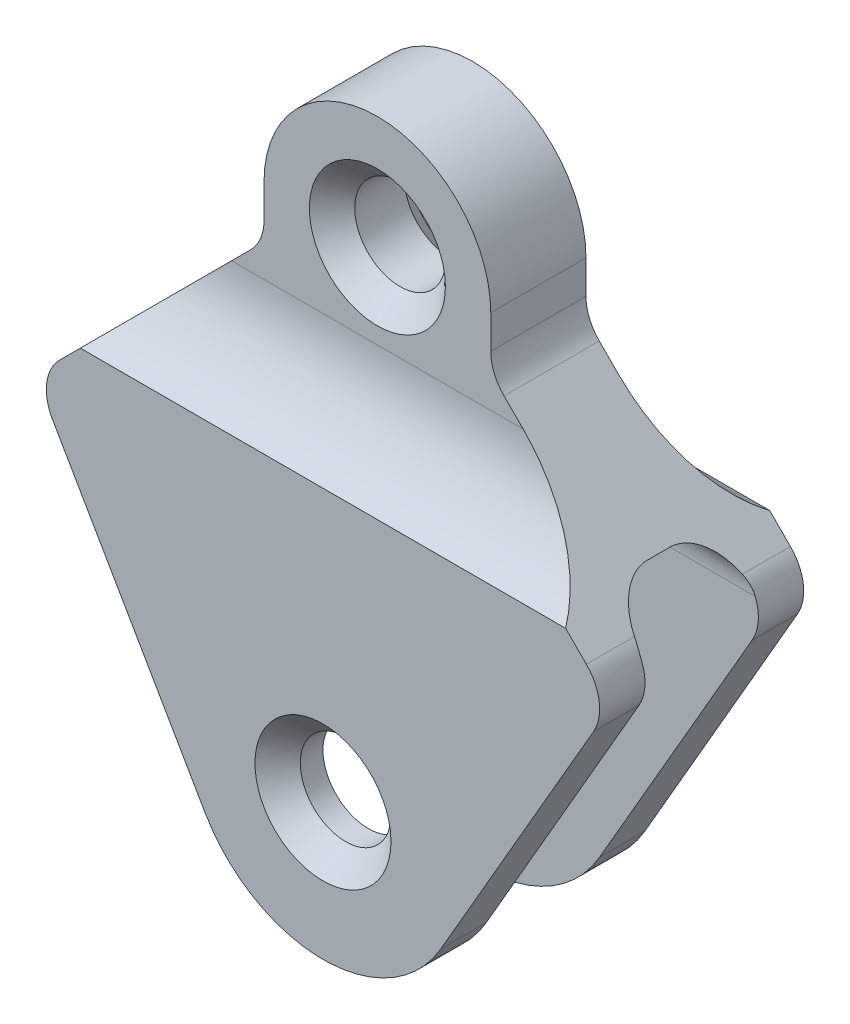
SolidWorks part; units mm, degrees
ref_plane "Front Plane" through (0, 0, 0) normal (0, 0, 1) x (1, 0, 0)
ref_plane "Top Plane" through (0, 0, 0) normal (0, 1, 0) x (1, 0, 0)
ref_plane "Right Plane" through (0, 0, 0) normal (1, 0, 0) x (0, 0, -1)
sketch "Sketch1" plane through (0, 0, 0) normal (0, 0, 1) x (1, 0, 0)
  line L0 (-25, 0) -> (-25, -11.4915)
  line L1 (-25, -11.4915) -> (-63.5085, -50)
  line L2 (-63.5085, -50) -> (-25.9808, -115)
  line L3 (0, 25) -> (0, -130) construction
  line L4 (63.5085, -50) -> (25.9808, -115)
  line L5 (25, -11.4915) -> (63.5085, -50)
  line L6 (25, 0) -> (25, -11.4915)
  circle A0 centre (0, 0) radius 10
  circle A1 centre (0, -100) radius 10
  arc A2 (25, 0) -> (-25, 0) centre (0, 0) ccw
  arc A3 (-25.9808, -115) -> (25.9808, -115) centre (0, -100) ccw
  point P17 (0, 0)
  dimension "D1" = 20
  dimension "D2" = 20
  dimension "D3" = 50
  dimension "D4" = 60
  dimension "D5" = 100
  dimension "D6" = 50
  dimension "D7" = 60
  dimension "D8" = 90
extrude "Boss-Extrude1" add sketch "Sketch1" against normal blind 45
sketch "Sketch2" plane through (0, 0, 0) normal (1, 0, 0) x (0, 0, -1)
  line L0 (0, -130) -> (45, -130) construction
  line L1 (10, -130) -> (35, -130)
  line L2 (10, -130) -> (10, -38)
  line L3 (10, -38) -> (35, -38)
  line L4 (35, -130) -> (35, -38)
  dimension "D1" = 92
  dimension "D2" = 25
  dimension "D3" = 10
extrude "Cut-Extrude1" cut sketch "Sketch2" against normal up to next and the other way up to next
fillet "Fillet2" radius 10 6 edges at (-25, -11.4915, -22.5) (25, -11.4915, -22.5) (-63.5085, -50, -40) (-63.5085, -50, -5) (63.5085, -50, -40) (63.5085, -50, -5)
fillet "Fillet3" radius 10 2 edges at (0, -38, -10) (0, -38, -35)
sketch "Sketch4" plane through (25, 0, 0) normal (1, 0, 0) x (0, 0, -1)
  line L0 (45, -40) -> (33, -40)
  line L5 (0, 25) -> (12, 25)
  line L11 (0, 25) -> (0, -40)
  line L18 (0, -40) -> (12, -40)
  line L19 (12, 25) -> (12, -40)
  line L20 (22.5, 25) -> (22.5, -129.3023) construction
  line L21 (45, 25) -> (0, 25) construction
  line L26 (33, 25) -> (33, -40)
  line L27 (45, 25) -> (33, 25)
  line L28 (45, 25) -> (45, -40)
  dimension "D2" = 65
  dimension "D1" = 12
extrude "Cut-Extrude5" cut sketch "Sketch4" against normal up to next and the other way up to next
fillet "Fillet4" radius 25 2 edges at (0, -40, -33) (0, -40, -12)
chamfer "Chamfer1" distance 5 angle 45 4 edges at (0, 10, -12) (0, -10, -33) (10, -100, -45) (10, -100, 0)
